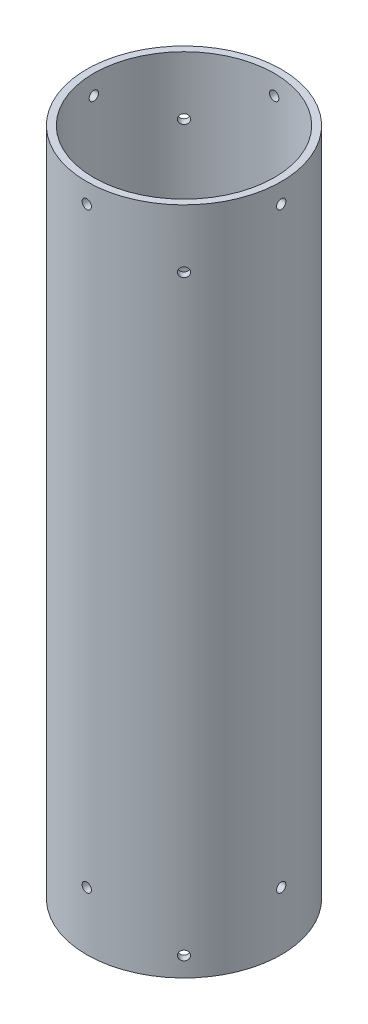
SolidWorks part; units mm, degrees
material "ПВХ 0.007 Смягченный"
ref_plane "Спереди" through (0, 0, 0) normal (0, 0, 1) x (1, 0, 0)
ref_plane "Сверху" through (0, 0, 0) normal (0, 1, 0) x (1, 0, 0)
ref_plane "Справа" through (0, 0, 0) normal (1, 0, 0) x (0, 0, -1)
sketch "Эскиз1" plane through (0, 0, 0) normal (0, 1, 0) x (1, 0, 0)
  circle A0 centre (0, 0) radius 25
  circle A1 centre (0, 0) radius 23.2
  dimension "ExDBody" = 50
  dimension "InDBody" = 46.4
extrude "Бобышка-Вытянуть1" add sketch "Эскиз1" along normal blind 172
ref_plane "Плоскость1" through (0, 31, 0) normal (0, -1, 0) x (-1, 0, 0)
sketch "Эскиз3" plane through (0, 0, 0) normal (1, 0, 0) x (0, 0, -1)
  line L0 (23.2, 172) -> (-23.2, 172) construction
  line L2 (-25, 0) -> (25, 0) construction
  circle A0 centre (0, 167) radius 1.2
  circle A3 centre (0, 15) radius 1.2
  dimension "D1" = 5
  dimension "D3" = 15
  dimension "D2" = 2.4
  dimension "D4" = 2.4
extrude "Вырез-Вытянуть2" cut sketch "Эскиз3" against normal through all
pattern_circular "Круговой массив1" count 4 over 360 about axis through (0, 172, 0) along (0, -1, 0) of "Вырез-Вытянуть2"
ref_plane "Плоскость2" through (0, 0, 0) normal (-0.7071, 0, 0.7071) x (0, -1, 0)
sketch "Эскиз11" plane through (0, 0, 0) normal (-0.7071, 0, 0.7071) x (0, -1, 0)
  line L0 (-172, 0) -> (0, 0) construction
  line L1 (0, -25) -> (0, 25) construction
  line L2 (-172, 25) -> (-172, -25) construction
  circle A0 centre (-5, 0) radius 1.2
  circle A1 centre (-157, 0) radius 1.2
  dimension "D1" = 2.4
  dimension "D3" = 15
  dimension "D4" = 2.4
  dimension "D2" = 5
extrude "Вырез-Вытянуть10" cut sketch "Эскиз11" against normal through all
pattern_circular "Круговой массив2" count 4 over 360 about axis through (0, 172, 0) along (0, -1, 0) of "Вырез-Вытянуть10"
sketch "Эскиз13" plane through (0, 0, 0) normal (-0.7071, 0, 0.7071) x (0, -1, 0)
  text T0 "Fire Way\r\n\r\n Spark" font "Blazed" height in points 40
